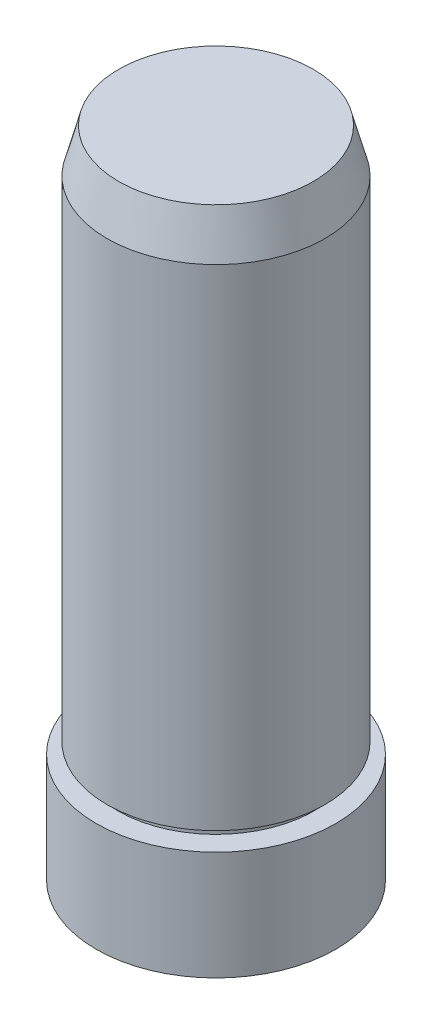
SolidWorks part; units mm, degrees
ref_plane "Спереди" through (0, 0, 0) normal (0, 0, 1) x (1, 0, 0)
ref_plane "Сверху" through (0, 0, 0) normal (0, 1, 0) x (1, 0, 0)
ref_plane "Справа" through (0, 0, 0) normal (1, 0, 0) x (0, 0, -1)
sketch "Эскиз1" plane through (0, 0, 0) normal (0, 1, 0) x (1, 0, 0)
  circle A0 centre (0, 0) radius 10
  dimension "D1" = 20
extrude "Бобышка-Вытянуть1" add sketch "Эскиз1" along normal blind 50
sketch "Эскиз2" plane through (0, 0, 0) normal (0, -1, 0) x (1, 0, 0)
  circle A0 centre (0, 0) radius 11
  dimension "D1" = 22
extrude "Бобышка-Вытянуть2" add sketch "Эскиз2" along normal blind 10
chamfer "Фаска1" distance 4 angle 15 1 edges at (0, 50, 10) first distance on face at (0, 50, 10)
sketch "Эскиз3" plane through (0, 0, 0) normal (0, 1, 0) x (1, 0, 0)
  circle A0 centre (0, 0) radius 10 construction
  circle A1 centre (0, 0) radius 10
  circle A2 centre (0, 0) radius 9
  dimension "D1" = 1
extrude "Вырез-Вытянуть1" cut sketch "Эскиз3" along normal blind 1
ref_plane "mouting-plane" through (0, 0, 10) normal (0, 0, 1) x (1, 0, 0)
equation "\"H\"=10"
equation "\"D\"=20"
equation "\"L\"=50"
equation "\"D1@Эскиз1\" = \"D\""
equation "\"D1@Эскиз2\" = 1.1*\"D\""
equation "\"D1@Бобышка-Вытянуть1\"=\"L\""
equation "\"D1@Бобышка-Вытянуть2\"=\"H\""
